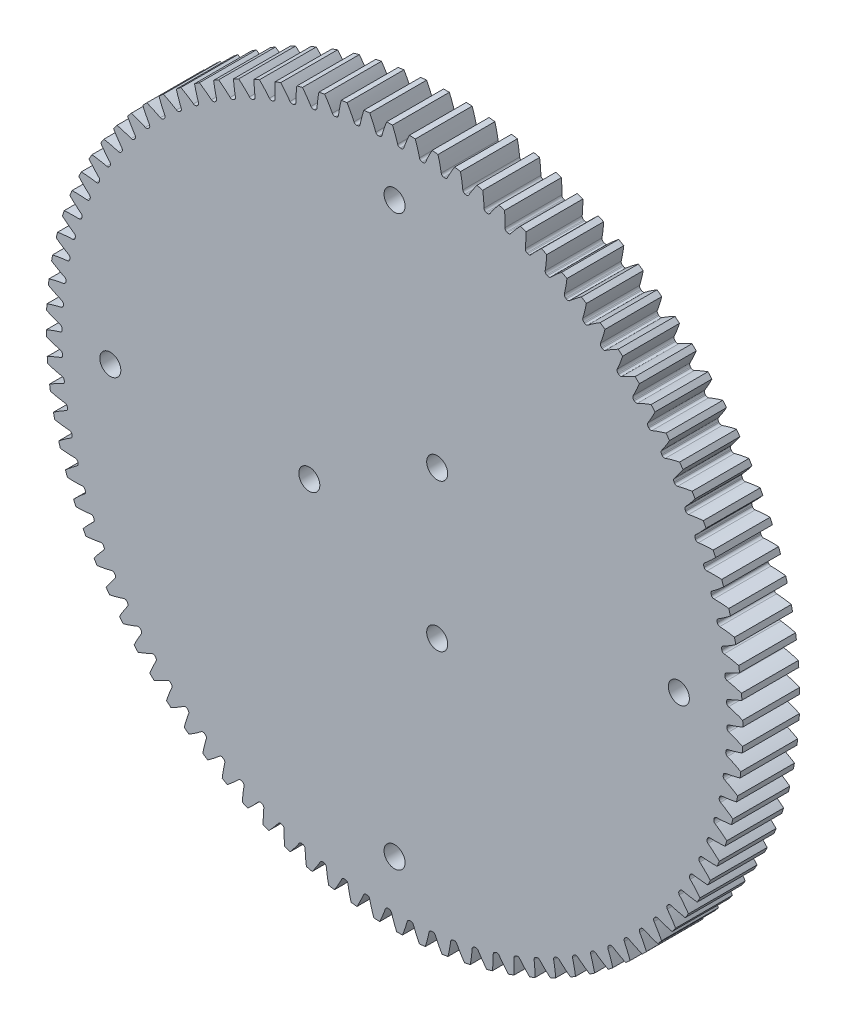
SolidWorks part; units mm, degrees
ref_plane "Front" through (0, 0, 0) normal (0, 0, 1) x (1, 0, 0)
ref_plane "Top" through (0, 0, 0) normal (0, 1, 0) x (1, 0, 0)
ref_plane "Right" through (0, 0, 0) normal (1, 0, 0) x (0, 0, -1)
sketch "Sketch3" plane through (0, 0, 0) normal (0, 0, 1) x (1, 0, 0)
  circle A0 centre (0, 0) radius 77.7875
  dimension "od" = 155.575
extrude "gearBody" add sketch "Sketch3" along normal blind 12.7
sketch "Sketch2" plane through (0, 0, 0) normal (0, 0, 1) x (1, 0, 0)
  line L0 (0, 0) -> (66.154, 27.4019) construction
  line L1 (89.9379, -14.1817) -> (0, 0) construction
  line L2 (0, 0) -> (36.3143, 0) construction
  line L3 (76.1998, -0.172) -> (76.1546, -2.6294) construction
  line L5 (76.1772, -1.4007) -> (0, 0) construction
  line L7 (0, 0) -> (71.6046, 0) construction
  arc A0 (71.5902, -1.4371) -> (71.5946, -1.1957) centre (0, 0) ccw construction
  arc A1 (77.7861, 0.4588) -> (77.7167, -3.3181) centre (0, 0) ccw construction
  arc A2 (76.1998, -0.172) -> (76.1546, -2.6294) centre (0, 0) ccw construction
  arc A3 (74.2296, -1.47) -> (74.2335, -1.2598) centre (0, 0) ccw
  arc A4 (89.9379, -14.1817) -> (74.6441, -2.0632) centre (65.1019, -29.8153) ccw
  arc A5 (89.9379, -14.1817) -> (90.3984, 10.8657) centre (0, 0) ccw
  arc A6 (90.3984, 10.8657) -> (74.6695, -0.6823) centre (66.154, 27.4019) cw
  arc A7 (74.2335, -1.2598) -> (74.6695, -0.6823) centre (74.8478, -1.2702) cw
  arc A8 (74.6441, -2.0632) -> (74.2296, -1.47) centre (74.8439, -1.4822) cw
  point P6 (90.3984, 10.8657)
  point P22 (89.9379, -14.1817)
  dimension "baseDia" = 143.2092
  dimension "od" = 155.575
  dimension "pd" = 152.4
  dimension "rd" = 148.4884
  dimension "rFillet" = 0.6144
  dimension "pointX" = 90.3984
  dimension "pointY" = 10.8657
  dimension "CTT" = 2.4574
  dimension "flankCenterAngle" = 22.5
extrude "toothCut" cut sketch "Sketch2" along normal through all
pattern_circular "CirPattern1" count 96 over 360 about axis through (0, 0, 12.7) along (0, 0, -1) of "toothCut"
sketch "hub1Dia" plane through (0, 0, 0) normal (0, 0, -1) x (-1, 0, 0)
  circle A0 centre (0, 0) radius 12.7
  dimension "hub1Dia" = 25.4
sketch "hub2Dia" plane through (0, 0, 12.7) normal (0, 0, 1) x (1, 0, 0)
  circle A0 centre (0, 0) radius 12.7
  dimension "hub2dia" = 25.4
sketch "boreDia" plane through (0, 0, 0) normal (0, 0, 1) x (1, 0, 0)
  circle A0 centre (0, 0) radius 7.9375
  dimension "boreDia" = 15.875
sketch "Sketch4" plane through (0, 0, 0) normal (0, 0, -1) x (-1, 0, 0)
  circle A0 centre (19.05, 0) radius 2.35
  circle A1 centre (-9.525, -16.4978) radius 2.35
  circle A2 centre (-9.525, 16.4978) radius 2.35
  point P10 (0, 0)
  dimension "D2" = 4.7
  dimension "D1" = 19.05
  dimension "D3" = 3
extrude "Cut-Extrude1" cut sketch "Sketch4" against normal through all
sketch "Sketch5" plane through (0, 0, 0) normal (0, 0, -1) x (-1, 0, 0)
  circle A0 centre (63.5, 0) radius 2.35
  circle A1 centre (0, -63.5) radius 2.35
  circle A2 centre (-63.5, 0) radius 2.35
  circle A3 centre (0, 63.5) radius 2.35
  point P12 (0, 0)
  dimension "D1" = 4.7
  dimension "D2" = 63.5
  dimension "D3" = 4
extrude "Cut-Extrude2" cut sketch "Sketch5" against normal through all
equation "\"D2@Sketch4\"=4.7mm"
equation "\"D1@Sketch5\"=4.7mm"
